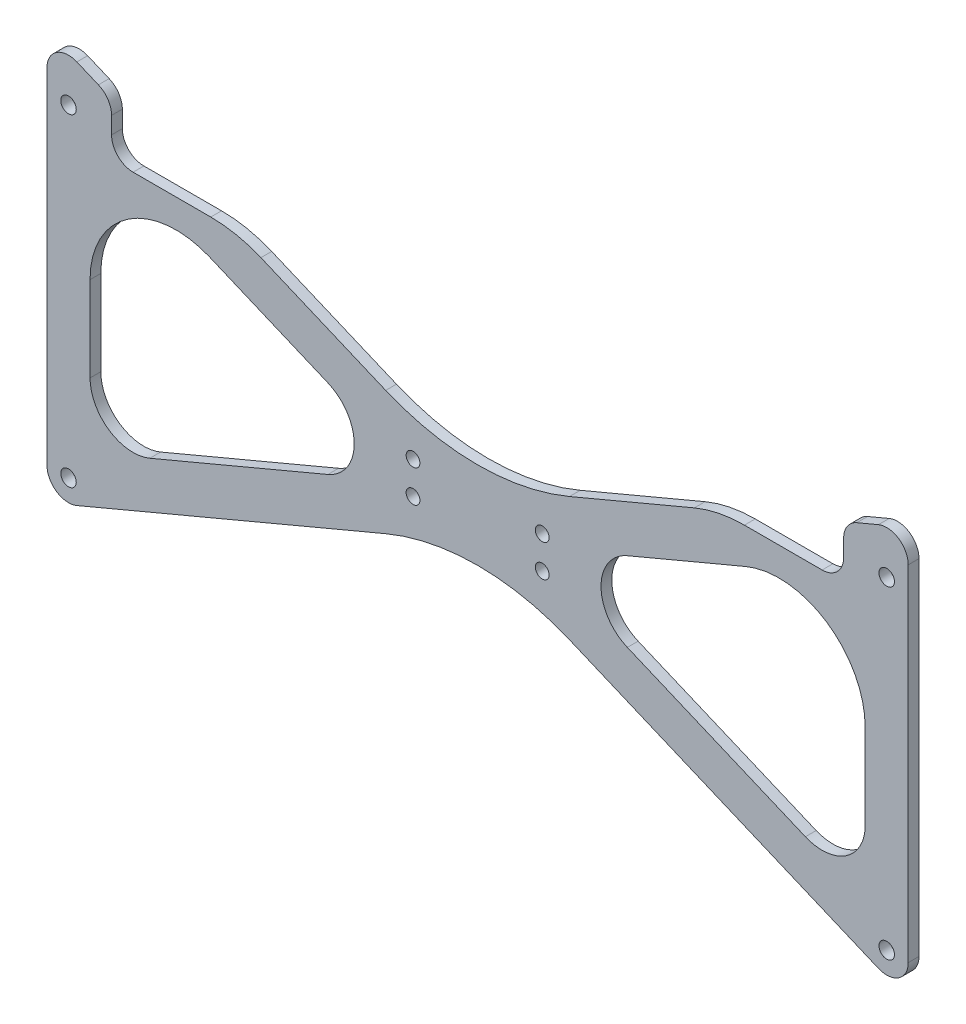
SolidWorks part; units mm, degrees
ref_plane "Front Plane" through (0, 0, 0) normal (0, 0, 1) x (1, 0, 0)
ref_plane "Top Plane" through (0, 0, 0) normal (0, 1, 0) x (1, 0, 0)
ref_plane "Right Plane" through (0, 0, 0) normal (1, 0, 0) x (0, 0, -1)
sketch "Sketch1" plane through (0, 0, 0) normal (0, 0, 1) x (1, 0, 0)
  line L0 (-120.65, -50.8) -> (120.65, 50.8) construction
  line L3 (-114.3, -41.2364) -> (-16.3636, 0)
  line L11 (-120.65, 50.8) -> (120.65, -50.8) construction
  line L12 (-118.1858, 56.6524) -> (0, 6.8899)
  line L13 (-114.3, 41.2364) -> (-16.3636, 0)
  line L14 (0, 6.8899) -> (118.1858, 56.6524)
  line L16 (16.3636, 0) -> (114.3, 41.2364)
  line L17 (16.3636, 0) -> (114.3, -41.2364)
  line L18 (-127, 50.8) -> (-127, -50.8)
  line L19 (-114.3, 41.2364) -> (-114.3, -41.2364)
  line L20 (127, 50.8) -> (127, -50.8)
  line L21 (114.3, 41.2364) -> (114.3, -41.2364)
  line L28 (-118.1858, -56.6524) -> (0, -6.8899)
  line L30 (0, -6.8899) -> (118.1858, -56.6524)
  arc A4 (-127, -50.8) -> (-118.1858, -56.6524) centre (-120.65, -50.8) ccw
  arc A5 (127, 50.8) -> (118.1858, 56.6524) centre (120.65, 50.8) ccw
  arc A6 (-118.1858, 56.6524) -> (-127, 50.8) centre (-120.65, 50.8) ccw
  arc A7 (118.1858, -56.6524) -> (127, -50.8) centre (120.65, -50.8) ccw
  point P2 (0, 0)
  point P9 (0, 0)
  point P13 (0, 0)
  point P26 (0, 0)
  dimension "D1" = 254
  dimension "D3" = 6.35
  dimension "D2" = 101.6
  dimension "D5" = 12.7
extrude "Boss-Extrude1" add sketch "Sketch1" along normal blind 3.175
sketch "Sketch2" plane through (0, 0, 3.175) normal (0, 0, 1) x (1, 0, 0)
  circle A0 centre (-120.65, 44.45) radius 2.286
  circle A1 centre (-120.65, -50.8) radius 2.286
  circle A2 centre (120.65, -50.8) radius 2.286
  circle A3 centre (120.65, 44.45) radius 2.286
  arc A5 (-127, -50.8) -> (-118.1858, -56.6524) centre (-120.65, -50.8) ccw construction
  arc A6 (118.1858, -56.6524) -> (127, -50.8) centre (120.65, -50.8) ccw construction
  circle A8 centre (-120.65, 44.45) radius 1.905 construction
  circle A9 centre (120.65, 44.45) radius 1.905 construction
  dimension "D1" = 4.572
extrude "Cut-Extrude1" cut sketch "Sketch2" against normal through all
fillet "Fillet1" radius 12.7 4 edges at (114.3, -41.2364, 1.5875) (16.3636, 0, 1.5875) (-114.3, -41.2364, 1.5875) (-16.3636, 0, 1.5875)
fillet "Fillet5" radius 69.85 2 edges at (0, -6.8899, 1.5875) (0, 6.8899, 1.5875)
fillet "Fillet8" radius 25.4 2 edges at (114.3, 41.2364, 1.5875) (-114.3, 41.2364, 1.5875)
sketch "Sketch5" plane through (0, 0, 3.175) normal (0, 0, 1) x (1, 0, 0)
  circle A0 centre (-19.05, 4.7625) radius 2.032
  circle A1 centre (-19.05, -4.7625) radius 2.032
  point P4 (0, 0)
  dimension "D2" = 4.064
  dimension "D1" = 9.525
  dimension "D3" = 19.05
extrude "Cut-Extrude3" cut sketch "Sketch5" against normal through all
mirror "Mirror1" about plane through (0, 0, 0) normal (1, 0, 0) of "Cut-Extrude3"
sketch "Sketch6" plane through (0, 0, 3.175) normal (0, 0, 1) x (1, 0, 0)
  line L6 (-107.95, 52.3426) -> (-107.95, 36.7851)
  line L8 (-27.1058, 18.3029) -> (-118.1858, 56.6524) construction
  line L9 (-107.95, 36.7851) -> (-71.0009, 36.7851)
  line L12 (-127, 50.8) -> (-127, -50.8) construction
  line L13 (-71.0009, 36.7851) -> (-107.95, 52.3426)
  point P6 (-71.0009, 36.7851)
  dimension "D1" = 15.5575
  dimension "D2" = 19.05
extrude "Cut-Extrude4" cut sketch "Sketch6" against normal through all contours L6 L9 L13
mirror "Mirror2" about plane through (0, 0, 0) normal (1, 0, 0) of "Cut-Extrude4"
fillet "Fillet6" radius 6.35 4 edges at (-107.95, 52.3426, 1.5875) (-107.95, 36.7851, 1.5875) (107.95, 52.3426, 1.5875) (107.95, 36.7851, 1.5875)
fillet "Fillet9" radius 38.1 2 edges at (71.0009, 36.7851, 1.5875) (-71.0009, 36.7851, 1.5875)
